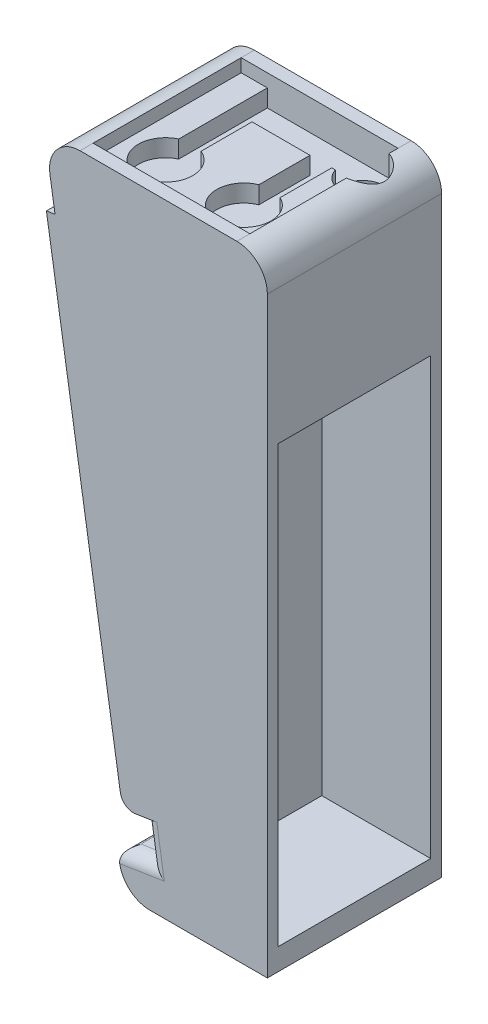
SolidWorks part; units mm, degrees
ref_plane "Front Plane" through (0, 0, 0) normal (0, 0, 1) x (1, 0, 0)
ref_plane "Top Plane" through (0, 0, 0) normal (0, 1, 0) x (1, 0, 0)
ref_plane "Right Plane" through (0, 0, 0) normal (1, 0, 0) x (0, 0, -1)
sketch "Sketch1" plane through (0, 0, 0) normal (0, 0, 1) x (1, 0, 0)
  line L4 (-46.5725, -83.7419) -> (-67.7766, 50.1096)
  line L5 (-50.5725, -92.8661) -> (-16.5725, -92.8661)
  line L9 (-50.5725, -83.7419) -> (-46.5725, -83.7419)
  line L10 (-50.5725, -83.7419) -> (-50.5725, -92.8661)
  line L13 (-16.5725, -92.8661) -> (-16.5725, 50.1096)
  line L14 (-67.7766, 50.1096) -> (-16.5725, 50.1096)
  dimension "D1" = 51.2041
  dimension "D4" = 9.1242
  dimension "D5" = 34
  dimension "D6" = 4
extrude "Boss-Extrude1" add sketch "Sketch1" along normal blind 40
fillet "Fillet3" radius 7 1 edges at (-50.5725, -92.8661, 20) type face fillet first side face at (-33.5725, -92.8661, 20) second side face at (-50.5725, -88.304, 20)
fillet "Fillet4" radius 7 1 edges at (-16.5725, 50.1096, 20) type face fillet first side face at (-42.1745, 50.1096, 20) second side face at (-16.5725, -21.3782, 20)
fillet "Fillet5" radius 7 1 edges at (-67.7766, 50.1096, 20) type face fillet first side face at (-45.6745, 50.1096, 20) second side face at (-57.1745, -16.8161, 20)
sketch "Sketch8" plane through (-58.3736, -9.2472, 0) normal (-0.9877, -0.1565, 0) x (0, 0, 1)
  line L0 (40, 51.9009) -> (40, -75.4236) construction
  line L1 (0, -75.4236) -> (40, -75.4236)
  line L2 (0, -75.4236) -> (0, 44.4009)
  line L3 (0, 44.4009) -> (40, 44.4009)
  line L4 (40, -75.4236) -> (40, 44.4009)
  line L5 (40, 51.9009) -> (0, 51.9009) construction
  dimension "D1" = 7.5
extrude "Boss-Extrude2" add sketch "Sketch8" along normal blind 2
sketch "Sketch9" plane through (-60.3489, -9.5602, 0) normal (-0.9877, -0.1565, 0) x (0, 0, 1)
  line L0 (20, -75.1068) -> (20, -33.9113) construction
  line L1 (0, -75.1068) -> (40, -75.1068) construction
  line L2 (40, -75.1068) -> (40, 44.4009) construction
  line L3 (0, -67.1068) -> (40, -67.1068)
  line L4 (0, -67.1068) -> (0, -75.1068)
  line L5 (0, -75.1068) -> (40, -75.1068)
  line L6 (40, -67.1068) -> (40, -75.1068)
  line L7 (0, -67.1068) -> (40, -75.1068) construction
  line L8 (0, -75.1068) -> (40, -67.1068) construction
  point P4 (20, -71.1068)
  dimension "D1" = 8
extrude "Cut-Extrude6" cut sketch "Sketch9" against normal blind 5
fillet "Fillet6" radius 3 2 edges at (-50.5725, -83.7419, 20) (-49.8491, -75.8404, 20)
fillet "Fillet7" radius 3 4 edges at (-44.2849, -79.0088, 0) (-44.2849, -79.0088, 40) (-46.1282, -83.3507, 0) (-46.1282, -83.3507, 40)
sketch "Sketch10" plane through (-16.5725, 0, 0) normal (1, 0, 0) x (0, 0, -1)
  line L1 (-37.5, -87.8661) -> (-2.5, -87.8661)
  line L2 (-37.5, -87.8661) -> (-37.5, 12.1339)
  line L3 (-37.5, 12.1339) -> (-2.5, 12.1339)
  line L4 (-2.5, -87.8661) -> (-2.5, 12.1339)
  line L5 (-40, -92.8661) -> (0, -92.8661) construction
  line L6 (-40, -92.8661) -> (-40, 43.1096) construction
  dimension "D1" = 100
  dimension "D2" = 5
  dimension "D3" = 35
  dimension "D4" = 2.5
extrude "Cut-Extrude7" cut sketch "Sketch10" against normal blind 25
sketch "Sketch11" plane through (0, 12.1339, 0) normal (0, -1, 0) x (1, 0, 0)
  line L0 (-30.0725, 40) -> (-30.0725, 0) construction
  line L1 (-43.5725, 40) -> (-16.5725, 40) construction
  line L2 (-43.5725, 0) -> (-16.5725, 0) construction
  line L3 (-23.5725, 0) -> (-59.5804, 0) construction
  circle A0 centre (-24.6922, 10) radius 5
  dimension "D1" = 10
  dimension "D2" = 10
extrude "Cut-Extrude8" cut sketch "Sketch11" against normal blind 40
sketch "Sketch12" plane through (0, 50.1096, 0) normal (0, 1, 0) x (1, 0, 0)
  line L0 (-66.5804, -20) -> (-16.5725, -20) construction
  line L1 (-66.5804, 0) -> (-66.5804, -40) construction
  line L2 (-16.5725, 0) -> (-16.5725, -40) construction
  line L3 (-23.5725, -5.127) -> (-23.5725, 0) construction
  line L4 (-59.5804, -37) -> (-23.5725, -37)
  line L5 (-59.5804, -37) -> (-59.5804, -3)
  line L6 (-59.5804, -3) -> (-23.5725, -3)
  line L7 (-23.5725, -37) -> (-23.5725, -3)
  line L8 (-59.5804, -37) -> (-23.5725, -3) construction
  line L9 (-59.5804, -3) -> (-23.5725, -37) construction
  line L10 (-23.5725, 0) -> (-59.5804, 0) construction
  point P6 (-41.5764, -20)
  dimension "D1" = 3
extrude "Cut-Extrude9" cut sketch "Sketch12" against normal blind 3
sketch "Sketch14" plane through (0, 47.1096, 0) normal (0, 1, 0) x (1, 0, 0)
  line L0 (-16.5725, -20) -> (-67.2961, -20) construction
  line L1 (-16.5725, 0) -> (-16.5725, -40) construction
  line L2 (-67.2961, -40) -> (-67.2961, 0) construction
  line L3 (-41.9343, -20) -> (-41.9477, -40) construction
  line L4 (-59.5804, -3) -> (-59.5804, -37) construction
  line L6 (-48.5804, -23.2127) -> (-48.5804, -9)
  line L7 (-48.5804, -9) -> (-53.5804, -9)
  line L8 (-53.5804, -23.335) -> (-53.5804, -9)
  line L9 (-35.2734, -9.0089) -> (-30.2734, -9.0156)
  line L10 (-30.2926, -23.3506) -> (-30.2734, -9.0156)
  line L12 (-35.2925, -23.2216) -> (-35.2734, -9.0089)
  arc A0 (-53.5804, -23.335) -> (-48.5804, -23.2127) centre (-50.9403, -29) ccw
  arc A1 (-30.2926, -23.3506) -> (-35.2925, -23.2216) centre (-32.9403, -29.0121) cw
  dimension "D1" = 12.5
  dimension "D2" = 9
  dimension "D3" = 9
  dimension "D4" = 5
  dimension "D7" = 6
extrude "Cut-Extrude10" cut sketch "Sketch14" against normal blind 4
sketch "Sketch15" plane through (0, 47.1096, 0) normal (0, 1, 0) x (1, 0, 0)
  line L0 (-53.5804, -9) -> (-53.5804, -23.335) construction
  line L1 (-53.5804, -11.5074) -> (-23.5725, -11.5074)
  line L2 (-53.5804, -11.5074) -> (-53.5804, -3)
  line L3 (-53.5804, -3) -> (-23.5725, -3)
  line L4 (-23.5725, -11.5074) -> (-23.5725, -3)
extrude "Cut-Extrude12" cut sketch "Sketch15" against normal blind 4
